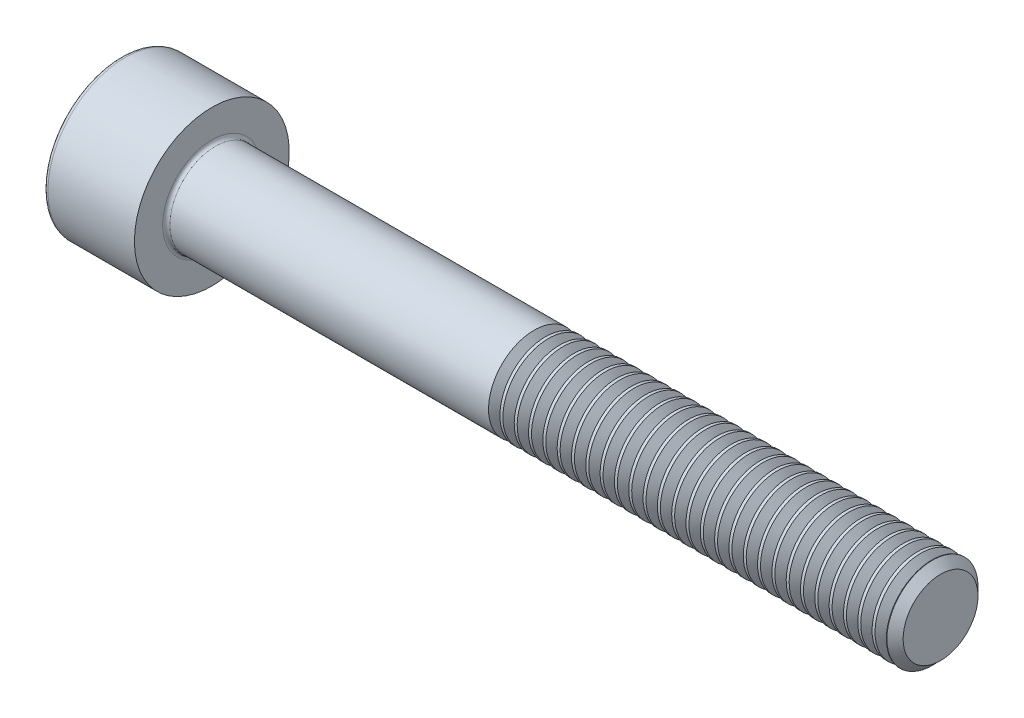
SolidWorks part; units mm, degrees
revolve "Base-Revolve" add sketch "BodySke"
sketch "BodySke" plane through (0, 0, 0) normal (0, 0, 1) x (1, 0, 0)
  line L0 (0, 0) -> (0, 4.25)
  line L1 (0, 4.25) -> (5, 4.25)
  line L2 (5, 4.25) -> (5, 2.5)
  line L3 (5, 2.5) -> (44.555, 2.5)
  line L4 (45, 2.055) -> (45, 0)
  line L5 (45, 0) -> (0, 0)
  line L6 (-31.75, 0) -> (127, 0) construction
  line L8 (45, 2.055) -> (44.555, 2.5)
  line L10 (45, -2.055) -> (44.555, -2.5) construction
  line L11 (5.8, 9.525) -> (5.8, 3.175) construction
  line L12 (23, 9.525) -> (23, 3.175) construction
  line L13 (-15, 9.525) -> (-15, 3.175) construction
  dimension "Diameter" = 5
  dimension "Head_dia" = 8.5
cosmetic thread "ThreadCosmetic" [suppressed]
fillet "Fillet1" radius 0.2 1 edges at (5, 0, 2.5)
fillet "Fillet2" radius 0.25 1 edges at (0, 0, 4.25)
ref_plane "Plane1" through (0, 0, 0) normal (0, 0, 1) x (1, 0, 0)
ref_plane "Plane2" through (0, 0, 0) normal (0, 1, 0) x (1, 0, 0)
ref_plane "Plane3" through (0, 0, 0) normal (1, 0, 0) x (0, 0, -1)
sketch "Sketch2" plane through (0, 0, 0) normal (0, 0, 1) x (1, 0, 0)
  line L0 (0, 2.042) -> (2.5, 2.042)
  line L1 (2.5, 2.042) -> (3.6789, 0)
  line L2 (-31.75, 0) -> (127, 0) construction
  line L3 (3.6789, 0) -> (0, 0)
  line L4 (0, 0) -> (0, 2.042)
  line L6 (0, 0) -> (47.625, 0) construction
  dimension "D1" = 2.042
  dimension "D2" = 60
revolve "Hex-PreBroach" cut sketch "Sketch2" angle 360 about L6
sketch "Sketch3" plane through (0, 0, 0) normal (-1, 0, 0) x (0, 0.5, 0.866)
  line L0 (1.1789, 2.042) -> (-1.1789, 2.042)
  line L1 (-1.1789, 2.042) -> (-2.3579, 0)
  line L2 (1.1789, 2.042) -> (2.3579, 0)
  line L3 (1.1789, -2.042) -> (2.3579, 0)
  line L4 (1.1789, -2.042) -> (-1.1789, -2.042)
  line L5 (-1.1789, -2.042) -> (-2.3579, 0)
  dimension "D1" = 2.042
  dimension "D2" = 2.042
extrude "Hex" cut sketch "Sketch3" against normal blind 2.5
sketch "ThdSchSke" plane through (0, 0, 0) normal (0, 0, 1) x (1, 0, 0)
  line L0 (23, -2.055) -> (22.6884, -2.5)
  line L1 (23, -2.055) -> (23.3116, -2.5)
  line L2 (23.3116, -2.5) -> (23.3116, -3.125)
  line L3 (-3.175, 0) -> (5.1513, 0) construction
  line L4 (0, 4) -> (0, -4) construction
  line L5 (23.3116, -3.125) -> (22.6884, -3.125)
  line L6 (22.6884, -3.125) -> (22.6884, -2.5)
  dimension "Diameter" = 5
  dimension "Thread_minor" = 4.11
  dimension "Start" = 23
revolve "ThreadSchematic" cut sketch "ThdSchSke" angle 360 about L3
pattern_linear "ThdSchPat" count 29 spacing 0.7857 along (1, 0, 0) of "ThreadSchematic"
equation "\"D2@Sketch3\" = \"Hex_size@Sketch3\" / 2"
equation "\"D1@Sketch3\" = \"Hex_size@Sketch3\" / 2"
equation "\"D1@Sketch2\" = \"Hex_size@Sketch3\" / 2"
equation "\"Thread_minor@ThreadCosmetic\"  =  \"Minor_dia@BodySke\""
equation "\"Depth@Sketch2\" =  \"Key_eng@Hex\""
equation "\"Thread_length@ThreadCosmetic\" = ((sgn( (\"Length@BodySke\" - \"Advance@BodySke\" * 3.0) - \"Thread_nom@BodySke\" )-1)*( (\"Length@BodySke\" - \"Advance@BodySke\" * 3.0) - \"Thread_nom@BodySke\" ))/-2+ \"Thread_nom@BodySke\""
equation "\"Thread_minor@ThdSchSke\" = \"Minor_dia@BodySke\""
equation "\"Diameter@ThdSchSke\" = \"Diameter@BodySke\""
equation "\"Overcut@ThdSchSke\" = \"Diameter@BodySke\" * 1.25"
equation "\"Start@ThdSchSke\" = \"Head_ht@BodySke\" + \"Length@BodySke\" - \"Thread_length@ThreadCosmetic\"  '---Non-countersunk---"
equation "\"Num_threads@ThdSchPat\" = int( \"Thread_length@ThreadCosmetic\" / \"Advance@BodySke\" + 0.999 )  + 1"
equation "\"Advance@ThdSchPat\" = \"Thread_length@ThreadCosmetic\" /  (\"Num_threads@ThdSchPat\" - 1) 'relax it"
equation "\"Num_threads@ThdSchPat\" = \"Num_threads@ThdSchPat\" - sgn( \"Num_threads@ThdSchPat\" - 1) '---chamfered tips only---"
